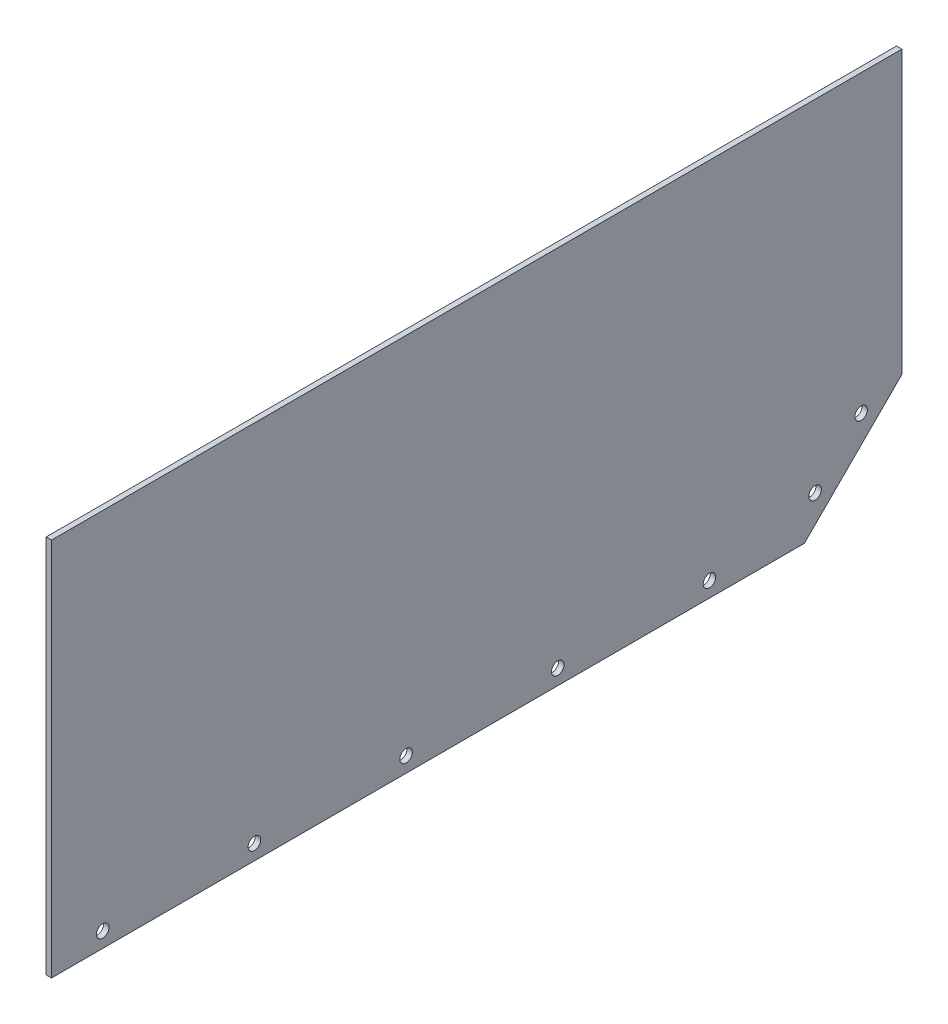
SolidWorks part; units mm, degrees
material "6061-T6 (SS)"
ref_plane "X-Y Datum" through (0, 0, 0) normal (0, 0, 1) x (1, 0, 0)
ref_plane "X-Z Datum" through (0, 0, 0) normal (0, 1, 0) x (1, 0, 0)
ref_plane "Y-Z Datum" through (0, 0, 0) normal (1, 0, 0) x (0, 0, -1)
sketch "Sketch1" plane through (0, 0, 0) normal (1, 0, 0) x (0, 0, -1)
  line L1 (-249.174, 82.55) -> (249.174, 82.55)
  line L2 (-249.174, 82.55) -> (-249.174, -82.55)
  line L3 (-249.174, -82.55) -> (249.174, -82.55)
  line L4 (249.174, 82.55) -> (249.174, -82.55)
  line L5 (-249.174, 82.55) -> (249.174, -82.55) construction
  line L6 (-249.174, -82.55) -> (249.174, 82.55) construction
  point P0 (0, 0)
  dimension "D1" = 165.1
  dimension "D2" = 498.348
extrude "Boss-Extrude1" add sketch "Sketch1" along normal mid plane 3.175
sketch "Sketch2" plane through (1.5875, 0, 0) normal (1, 0, 0) x (0, 0, -1)
  line L3 (192.024, -139.7) -> (-249.174, -139.7)
  line L5 (-249.174, -82.55) -> (249.174, -82.55) construction
  line L6 (-249.174, -82.55) -> (249.174, -82.55)
  line L7 (-249.174, -82.55) -> (-249.174, -139.7)
  line L12 (192.024, -139.7) -> (249.174, -82.55)
  line M10 (-249.174, -82.55) -> (249.174, -82.55)
  dimension "D1" = 45
  dimension "D5" = 57.15
extrude "Boss-Extrude2" add sketch "Sketch2" against normal blind 3.175 contours L3 L12 M10 region at (1.5875, -110.5456, 13.9978)
sketch "Sketch3" plane through (1.5875, 0, 0) normal (1, 0, 0) x (0, 0, -1)
  line L0 (-219.202, -139.7) -> (-219.202, -130.81)
  line L1 (192.024, -139.7) -> (-249.174, -139.7) construction
  line L2 (-219.202, -130.81) -> (-249.174, -130.81)
  line L3 (-249.174, 82.55) -> (-249.174, -139.7) construction
  circle A0 centre (-219.202, -130.81) radius 3.675
  dimension "D1" = 29.972
  dimension "D2" = 8.89
extrude "Cut-Extrude1" cut sketch "Sketch3" against normal blind 3.175 contours L2 A0 L0 | L0 A0 L2 region at (1.5875, -132.3697, 220.7617) region at (1.5875, -130.2901, 218.6821)
pattern_linear "LPattern1" count 5 spacing 88.9 along (0, 0, -1) of "Cut-Extrude1"
sketch "Sketch4" plane through (1.5875, 0, 0) normal (1, 0, 0) x (0, 0, -1)
  line L0 (192.024, -139.7) -> (183.9418, -131.6178)
  line L1 (183.9418, -131.6178) -> (198.3102, -117.2494)
  circle A0 centre (198.3102, -117.2494) radius 3.675
extrude "Cut-Extrude2" cut sketch "Sketch4" against normal through all contours A0 region at (1.5875, -120.5486, -199.6768)
pattern_linear "LPattern2" count 2 spacing 38.1 along (0, 0.7071, -0.7071) of "Cut-Extrude2"
